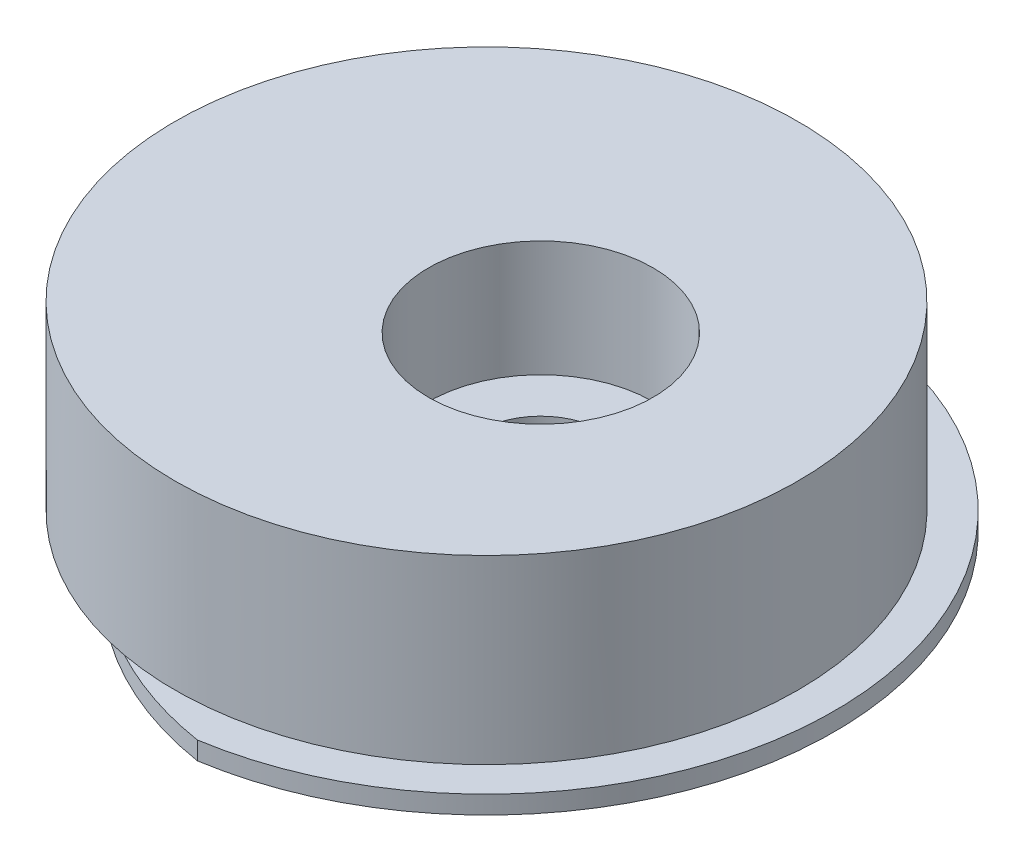
SolidWorks part; units mm, degrees
ref_plane "Front Plane" through (0, 0, 0) normal (0, 0, 1) x (1, 0, 0)
ref_plane "Top Plane" through (0, 0, 0) normal (0, 1, 0) x (1, 0, 0)
ref_plane "Right Plane" through (0, 0, 0) normal (1, 0, 0) x (0, 0, -1)
sketch "Sketch1" plane through (0, 0, 0) normal (0, 1, 0) x (1, 0, 0)
  line L0 (-3.025, 0) -> (3.025, 0) construction
  line L1 (0, -3.025) -> (0, 3.025) construction
  circle A0 centre (1.5, 0) radius 9.6
  circle A1 centre (-1.5, 0) radius 9.6
  dimension "D1" = 19.2
  dimension "D2" = 1.5
extrude "Boss-Extrude1" add sketch "Sketch1" along normal blind 0.5 contours A1 A0 region at (0, 0, 0)
sketch "Sketch2" plane through (0, 0.5, 0) normal (0, 1, 0) x (1, 0, 0)
  line L0 (-0.275, 0) -> (0.275, 0) construction
  line L1 (0, -0.275) -> (0, 0.275) construction
  circle A0 centre (-1.5, 0) radius 8.6
  dimension "D2" = 1.5
  dimension "D1" = 17.2
extrude "Boss-Extrude2" add sketch "Sketch2" along normal blind 5
sketch "Sketch3" plane through (0, 0, 0) normal (0, 1, 0) x (1, 0, 0)
  line L0 (0, -3.025) -> (0, 3.025) construction
  circle A0 centre (0, 5.8) radius 1.65
  circle A1 centre (0, -5.8) radius 1.35
  dimension "D1" = 3.3
  dimension "D3" = 2.7
  dimension "D2" = 5.8
  dimension "D4" = 5.8
extrude "Cut-Extrude1" cut sketch "Sketch3" along normal blind 4
sketch "Sketch4" plane through (0, 5.5, 0) normal (0, 1, 0) x (1, 0, 0)
  circle A0 centre (0, 0) radius 1.7
  dimension "D1" = 3.4
extrude "Cut-Extrude2" cut sketch "Sketch4" against normal through all
sketch "Sketch5" plane through (0, 5.5, 0) normal (0, 1, 0) x (1, 0, 0)
  circle A0 centre (0, 0) radius 3.1
  dimension "D1" = 6.2
extrude "Cut-Extrude3" cut sketch "Sketch5" against normal blind 3.2
equation "\"pin_circle_R\" = 27"
equation "\"ecc\" = 1.5"
equation "\"n_pins\" = 11"
equation "\"pin_d\" = 3"
equation "\"out_pin_R\" = 18.5"
equation "\"disc_clr\" = 0.1"
equation "\"seat_6803\" = 26.1"
equation "\"disc_t\" = 5"
equation "\"out_hole_clr\" = 0.5"
equation "\"boss_17\" = 17.20"
equation "\"rotor_bolt_R\" = 10"
equation "\"m25_clr\" = 2.8"
equation "\"m25_head\" = 5"
equation "\"insert_hole\" = 4.4"
equation "\"csk\" = 0.6"
equation "\"peg_d\" = 3.0"
equation "\"plug_d\" = 8.6"
equation "\"peg_clr\" = 0.3"
equation "\"m3_clr\" = 3.4"
equation "\"m3_head\" = 6.2"
equation "\"D2@Sketch1\"=\"ecc\""
equation "\"D1@Sketch2\"=\"boss_17\""
equation "\"D1@Sketch3\"=\"peg_d\"+\"peg_clr\""
equation "\"D3@Sketch3\"=\"peg_d\"-0.6+\"peg_clr\""
equation "\"D2@Sketch2\"=\"ecc\""
equation "\"D1@Sketch4\"=\"m3_clr\""
equation "\"D1@Sketch5\"=\"m3_head\""
equation "\"seat_6806\" = 42.1"
equation "\"pin_press\" = 3.2"
equation "\"pin_slip\" = 3.3"
equation "\"hub_30\" = 30.25"
equation "\"hub_short\" = 0.2"
equation "\"m3_tap\" = 2.8"
equation "\"rear_plate_t\" = 2"
equation "\"motor_ring\" = 40.4"
